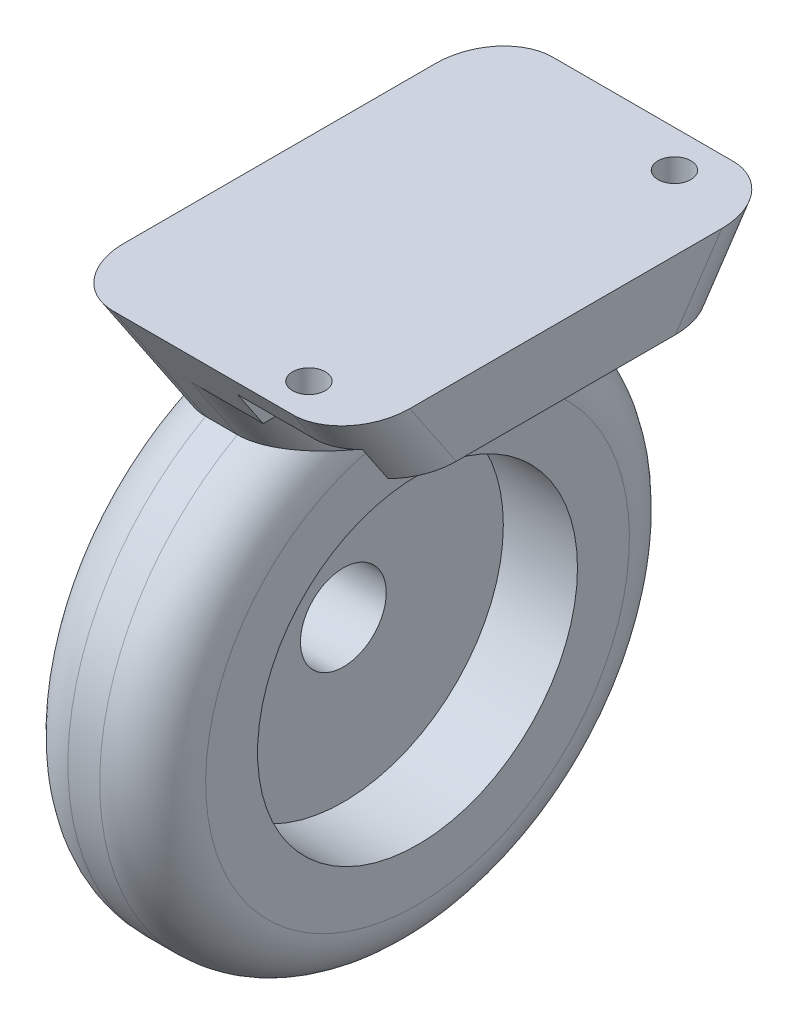
SolidWorks part; units mm, degrees
ref_plane "Front Plane" through (0, 0, 0) normal (0, 0, 1) x (1, 0, 0)
ref_plane "Top Plane" through (0, 0, 0) normal (0, 1, 0) x (1, 0, 0)
ref_plane "Right Plane" through (0, 0, 0) normal (1, 0, 0) x (0, 0, -1)
sketch "Sketch1" plane through (0, 0, 0) normal (1, 0, 0) x (0, 0, -1)
  line L0 (-20.75, 34.9317) -> (20.75, 34.9317)
  line L1 (-20.75, 34.9317) -> (-12, 21.9317)
  line L2 (20.75, 34.9317) -> (12, 21.9317)
  line L3 (-16.375, 28.4317) -> (16.375, 28.4317)
  circle A0 centre (0, 0) radius 25
  dimension "D1" = 50
  dimension "D2" = 41.5
  dimension "D3" = 12
  dimension "D4" = 13
extrude "Boss-Extrude1" add sketch "Sketch1" against normal blind 13 contours A0 | L1 L3 L2 L0 | A0 L2 L3 L1 region at (0, 31.8094, 0) region at (0, 26.1546, 0) region at (0, 0, 0)
sketch "Sketch2" plane through (0, 0, 0) normal (1, 0, 0) x (0, 0, -1)
  circle A0 centre (0, 0) radius 15.1
  dimension "D1" = 30.2
extrude "Cut-Extrude1" cut sketch "Sketch2" against normal blind 7
sketch "Sketch3" plane through (0, 0, 0) normal (1, 0, 0) x (0, 0, -1)
  circle A0 centre (0, 0) radius 4.05
  dimension "D1" = 8.1
extrude "Cut-Extrude2" cut sketch "Sketch3" against normal through all
extrude "Boss-Extrude3" add sketch "Sketch1<5>" along normal blind 14 contours L1 L3 L2 L0 region at (0, 31.8094, 0)
sketch "Sketch1<5>" plane through (0, 0, 0) normal (1, 0, 0) x (0, 0, -1) same geometry as "Sketch1"
sketch "Sketch4" plane through (0, 0, 0) normal (0, 1, 0) x (1, 0, 0)
  line L0 (-43.1002, 0) -> (40.5907, 0) construction
  line L2 (6.9543, 11.2502) -> (12.1731, 14.2105)
  line L3 (12.1731, 14.2105) -> (12.2189, 20.2103)
  line L4 (12.2189, 20.2103) -> (7.0457, 23.2498)
  line L5 (7.0457, 23.2498) -> (1.8269, 20.2895)
  line L6 (1.8269, 20.2895) -> (1.7811, 14.2897)
  line L7 (1.7811, 14.2897) -> (6.9543, 11.2502)
  line L8 (7, -23.25) -> (12.1962, -20.25)
  line L9 (12.1962, -20.25) -> (12.1962, -14.25)
  line L10 (12.1962, -14.25) -> (7, -11.25)
  line L11 (7, -11.25) -> (1.8038, -14.25)
  line L12 (1.8038, -14.25) -> (1.8038, -20.25)
  line L13 (1.8038, -20.25) -> (7, -23.25)
  circle A0 centre (7, -17.25) radius 1.55
  circle A1 centre (7, 17.25) radius 1.55
  circle A4 centre (7, 17.25) radius 5.1962 construction
  circle A5 centre (7, -17.25) radius 5.1962 construction
  dimension "D1" = 3.1
  dimension "D2" = 7
  dimension "D3" = 17.25
  dimension "D4" = 6
extrude "Cut-Extrude3" cut sketch "Sketch4" along normal through all contours A0 | A1 region at (7, 0, 17.25) region at (7, 0, -17.25)
extrude "Cut-Extrude4" cut sketch "Sketch4<4>" along normal blind 32
sketch "Sketch4<4>" plane through (0, 0, 0) normal (0, 1, 0) x (1, 0, 0) same geometry as "Sketch4"
fillet "Fillet1" radius 5 8 edges at (0, 25.1817, 14.1875) (0, 25.1817, -14.1875) (0, -25, 0) (14, 31.6817, 18.5625) (14, 31.6817, -18.5625) (-13, 28.4317, -16.375) (-13, 28.4317, 16.375) (-13, -25, 0)
equation "\"arm dia\"=50"
equation "\"D1@Sketch1\"=\"arm dia\""
equation "\"arm dist to attachment triangle\"=12"
equation "\"D3@Sketch1\"=\"arm dist to attachment triangle\""
equation "\"dist to top of attachment triangle\"=13"
equation "\"D4@Sketch1\"=\"dist to top of attachment triangle\""
equation "\"width of attachment triangle\"=41.5"
equation "\"D2@Sketch1\"=\"width of attachment triangle\""
equation "\"arm extrusion\"= 13"
equation "\"D1@Boss-Extrude1\"=\"arm extrusion\""
equation "\"gear extension OD\" = 30.2"
equation "\"D1@Sketch2\"=\"gear extension OD\""
equation "\"gear extension depth\"= 7"
equation "\"D1@Cut-Extrude1\"=\"gear extension depth\""
equation "\"bearing bore\"=8.1"
equation "\"D1@Sketch3\"=\"bearing bore\""
equation "\"D1@Boss-Extrude3\" = \"arm extrusion 2\""
equation "\"arm extrusion 2\"= 14"
equation "\"D2@Sketch4\"= \"arm extrusion 2\" / 2"
equation "\"M3 hole\"= 3.1"
equation "\"M3 hex nut\"= 6"
equation "\"D1@Sketch4\"= \"M3 hole\""
equation "\"hex nut extrusion depth\"=32"
equation "\"D1@Cut-Extrude4\"=\"hex nut extrusion depth\""
equation "\"D4@Sketch4\"=\"M3 hex nut\""
